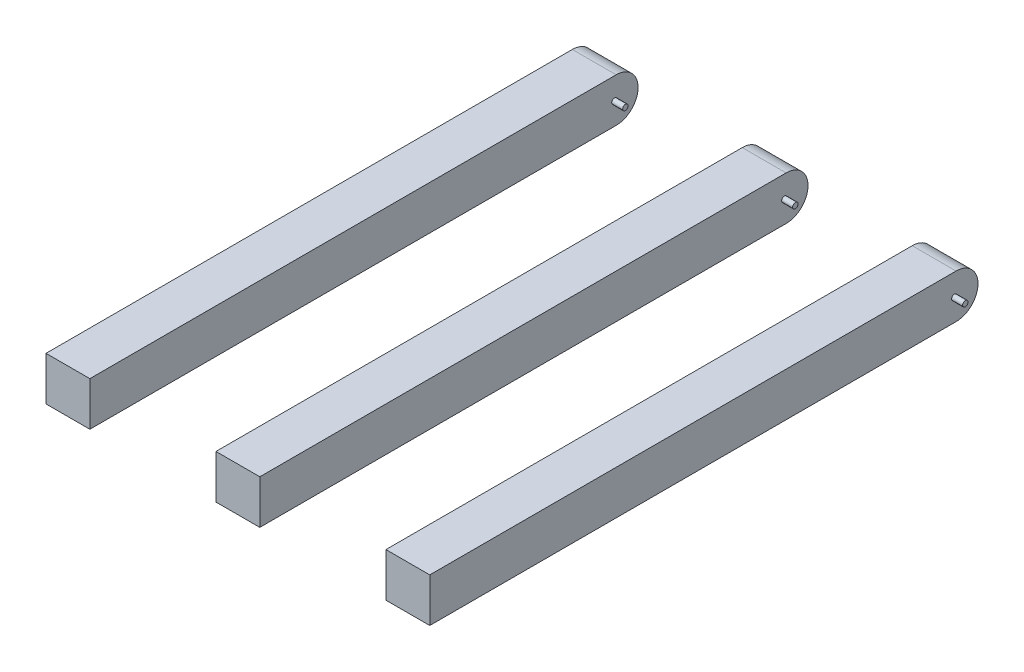
SolidWorks part; units mm, degrees
ref_plane "Front Plane" through (0, 0, 0) normal (0, 0, 1) x (1, 0, 0)
ref_plane "Top Plane" through (0, 0, 0) normal (0, 1, 0) x (1, 0, 0)
ref_plane "Right Plane" through (0, 0, 0) normal (1, 0, 0) x (0, 0, -1)
sketch "Sketch1" plane through (0, 0, 0) normal (0, 0, 1) x (1, 0, 0)
  line L0 (0, 0) -> (-59.8298, 0) construction
sketch "Sketch2" plane through (0, 0, 0) normal (0, 0, 1) x (1, 0, 0)
  line L1 (0.4, 0.4) -> (-0.4, 0.4)
  line L2 (0.4, 0.4) -> (0.4, -0.4)
  line L3 (0.4, -0.4) -> (-0.4, -0.4)
  line L4 (-0.4, 0.4) -> (-0.4, -0.4)
  line L5 (0.4, 0.4) -> (-0.4, -0.4) construction
  line L6 (0.4, -0.4) -> (-0.4, 0.4) construction
  point P0 (0, 0)
  dimension "D1" = 0.8
extrude "Boss-Extrude1" add sketch "Sketch2" along normal blind 10 contours L1 L4 L3 L2
sketch "Sketch3" plane through (0.4, 0, 0) normal (1, 0, 0) x (0, 0, -1)
  line L0 (0, 0.4) -> (0, -0.4) construction
  circle A0 centre (-0.4312, 0) radius 0.05
  dimension "D1" = 0.1
  dimension "D2" = 0.4312
extrude "Boss-Extrude2" add sketch "Sketch3" along normal blind 0.2
fillet "Fillet1" radius 0.4 2 edges at (0, -0.4, 0) (0, 0.4, 0)
pattern_linear "LPattern1" count 2 spacing 3.1 along (1, 0, 0) count 2 spacing 3.1 along (-1, 0, 0) of bodies 102
equation "\"Wire Thickness\"= 0.8mm"
equation "\"D1@Sketch2\"=\"Wire Thickness\""
equation "\"B\"= 0.93cm"
equation "\"D1@Boss-Extrude1\"=10mm"
equation "\"D1@Fillet1\"=\"Wire Thickness\"/2"
equation "\"D3@LPattern1\"=\"B\"/3"
